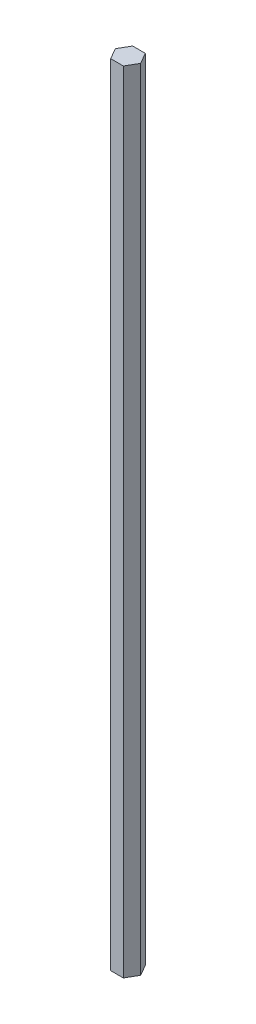
SolidWorks part; units mm, degrees
ref_plane "Front Plane" through (0, 0, 0) normal (0, 0, 1) x (1, 0, 0)
ref_plane "Top Plane" through (0, 0, 0) normal (0, 1, 0) x (1, 0, 0)
ref_plane "Right Plane" through (0, 0, 0) normal (1, 0, 0) x (0, 0, -1)
sketch "Sketch1" plane through (0, 0, 0) normal (0, 1, 0) x (1, 0, 0)
  line L7 (7.3323, 0) -> (3.6662, 6.35)
  line L8 (3.6662, 6.35) -> (-3.6662, 6.35)
  line L9 (-3.6662, 6.35) -> (-7.3323, 0)
  line L10 (-7.3323, 0) -> (-3.6662, -6.35)
  line L11 (-3.6662, -6.35) -> (3.6662, -6.35)
  line L12 (3.6662, -6.35) -> (7.3323, 0)
  circle A0 centre (0, 0) radius 6.35 construction
  dimension "D1" = 12.7
extrude "Boss-Extrude1" add sketch "Sketch1" along normal mid plane 457.2
sketch "Sketch3" plane through (0, 0, 0) normal (1, 0, 0) x (0, 0, -1)
  line L0 (0, 8.0656) -> (0, -8.0656) construction
  line L1 (0, 327.3297) -> (0, -319.0358) construction
